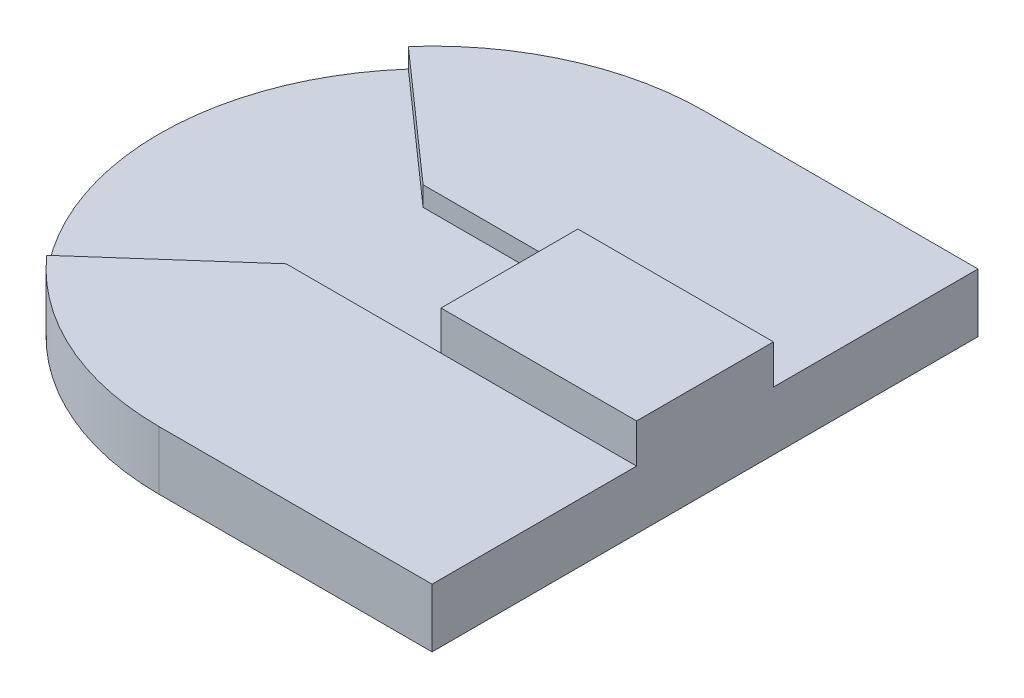
SolidWorks part; units mm, degrees
ref_plane "Front Plane" through (0, 0, 0) normal (0, 0, 1) x (1, 0, 0)
ref_plane "Top Plane" through (0, 0, 0) normal (0, 1, 0) x (1, 0, 0)
ref_plane "Right Plane" through (0, 0, 0) normal (1, 0, 0) x (0, 0, -1)
sketch "Sketch1" plane through (0, 0, 0) normal (0, 1, 0) x (1, 0, 0)
  line L0 (-10.4039, 13.9585) -> (-10.4039, -13.9585)
  line L1 (-10.4039, 13.9585) -> (3.5546, 13.9585)
  line L2 (-10.4039, -13.9585) -> (3.5546, -13.9585)
  line L3 (3.5546, 13.9585) -> (3.5546, -13.9585)
  line L4 (3.5546, 0) -> (-6.4454, 0)
  line L5 (3.5546, 0) -> (3.5546, 3.5)
  line L6 (-6.4454, 0) -> (-6.4454, 3.5)
  line L7 (3.5546, 3.5) -> (-6.4454, 3.5)
  line L8 (3.5546, 0) -> (-6.4454, 0)
  line L9 (3.5546, 0) -> (3.5546, -3.5)
  line L10 (-6.4454, 0) -> (-6.4454, -3.5)
  line L11 (3.5546, -3.5) -> (-6.4454, -3.5)
  line L12 (-6.4454, 3.5) -> (-10.4039, 0)
  line L13 (-10.4039, 0) -> (-20.8611, -9.2459)
  line L14 (-6.4454, -3.5) -> (-10.4039, 0)
  line L15 (-10.4039, 0) -> (-20.8611, 9.2459)
  line L16 (-6.4454, 3.5) -> (-14.3624, 3.5)
  line L17 (-6.4454, -3.5) -> (-14.3624, -3.5)
  circle A0 centre (-10.4039, 0) radius 13.9585
  dimension "D1" = 10
  dimension "D2" = 3.5
  dimension "D3" = 3.5
extrude "Boss-Extrude2" add sketch "Sketch1" along normal blind 2 contours L12 L16 L0 | L14 L10 L6 L12 | L17 L14 L0 | L0 L16 L15 | L15 A0 L13 | L17 L0 L13 region at (-9.0844, 0, -2.3333) region at (-11.7234, 0, -2.3333) region at (-18.9177, 0, 0) region at (-9.0844, 0, 2.3333) region at (-11.7234, 0, 2.3333) region at (-7.7649, 0, 0)
extrude "Boss-Extrude3" add sketch "Sketch1<5>" along normal blind 3 contours L0 A0 L15 L16 | L7 A0 L0 L16 | A0 L7 L3 L1 | L13 A0 L0 L17 | L0 A0 L11 L17 | A0 L2 L3 L11 region at (-4.9331, 0, -7.8559) region at (-14.3332, 0, -8.7736) region at (0.3994, 0, -10.9434) region at (-14.3332, 0, 8.7736) region at (-4.9331, 0, 7.8559) region at (0.3994, 0, 10.9434)
sketch "Sketch1<5>" plane through (0, 0, 0) normal (0, 1, 0) x (1, 0, 0) same geometry as "Sketch1"
extrude "Boss-Extrude5" add sketch "Sketch1<7>" along normal blind 5 contours L4 A0 L7 L6 | A0 L3 L7 | L11 A0 L4 L10 | A0 L11 L3 region at (-1.5183, 0, -1.7368) region at (3.4212, 0, -2.6278) region at (-1.5183, 0, 1.7368) region at (3.4212, 0, 2.6278)
sketch "Sketch1<7>" plane through (0, 0, 0) normal (0, 1, 0) x (1, 0, 0) same geometry as "Sketch1"
